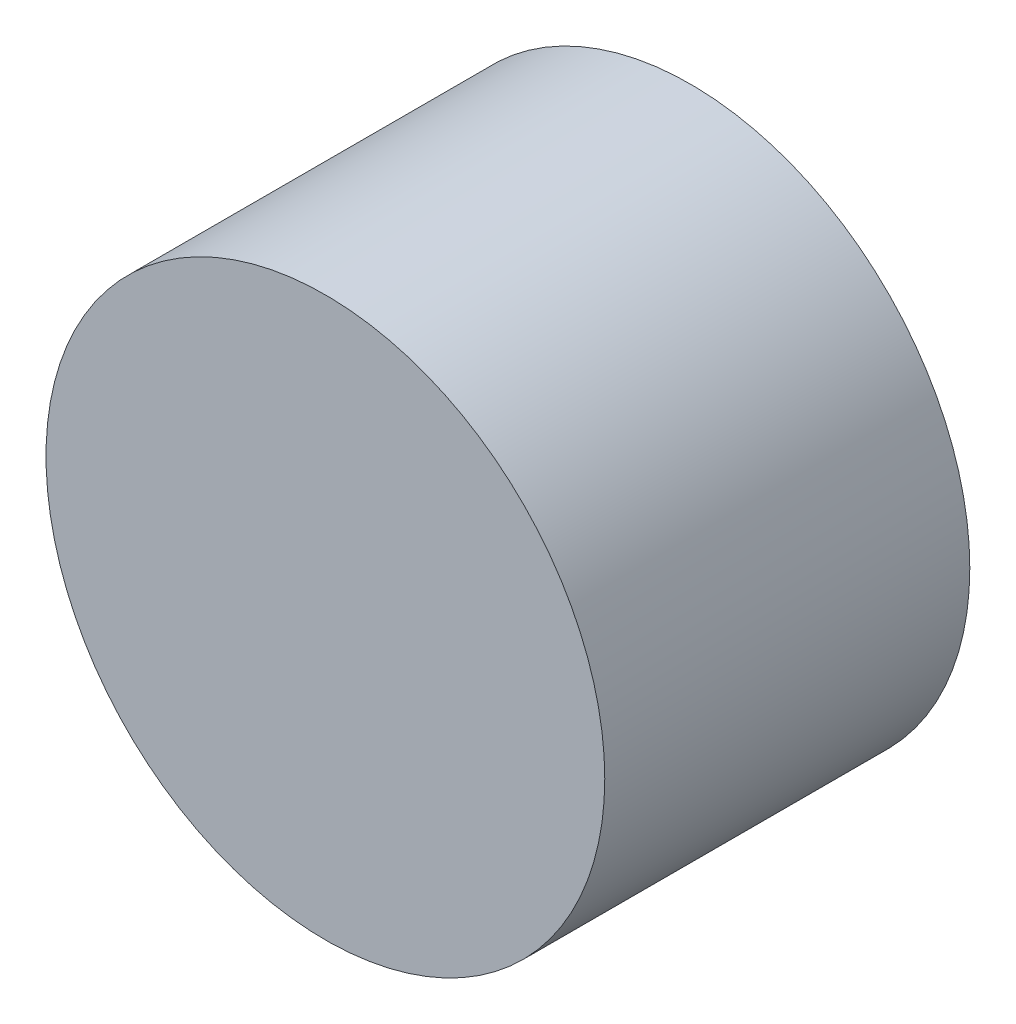
SolidWorks part; units mm, degrees
ref_plane "Front Plane" through (0, 0, 0) normal (0, 0, 1) x (1, 0, 0)
ref_plane "Top Plane" through (0, 0, 0) normal (0, 1, 0) x (1, 0, 0)
ref_plane "Right Plane" through (0, 0, 0) normal (1, 0, 0) x (0, 0, -1)
sketch "Sketch2" plane through (0, 0, 0) normal (0, 0, 1) x (1, 0, 0)
  circle A0 centre (0, 0) radius 107.15
  dimension "D1" = 214.3
extrude "Boss-Extrude2" add sketch "Sketch2" along normal blind 70 and the other way blind 70
sketch "Sketch3" plane through (0, 0, 70) normal (0, 0, 1) x (1, 0, 0)
  circle A0 centre (0, 0) radius 105.65
  dimension "D1" = 211.3
ref_plane "Plane2" through (0, 0, 45) normal (0, 0, 1) x (1, 0, 0)
ref_plane "Plane3" through (0, 107.15, 0) normal (0, 1, 0) x (1, 0, 0)
sketch "Sketch8" plane through (0, 107.15, 0) normal (0, 1, 0) x (1, 0, 0)
  line L0 (0, 70) -> (0, -40)
  line L1 (107.15, 70) -> (-107.15, 70) construction
  line L2 (0, -181.6691) -> (0, 181.6691) construction
  dimension "D1" = 110
ref_plane "Plane4" through (0, 107.15, 40) normal (0, 0, 1) x (1, 0, 0)
ref_axis "Axis1" through (60.5, 107.15, 40) along (-1, 0, 0)
ref_plane "Plane5" through (0, 51.1095, -37.1332) normal (0, -0.809, 0.5878) x (1, 0, 0)
